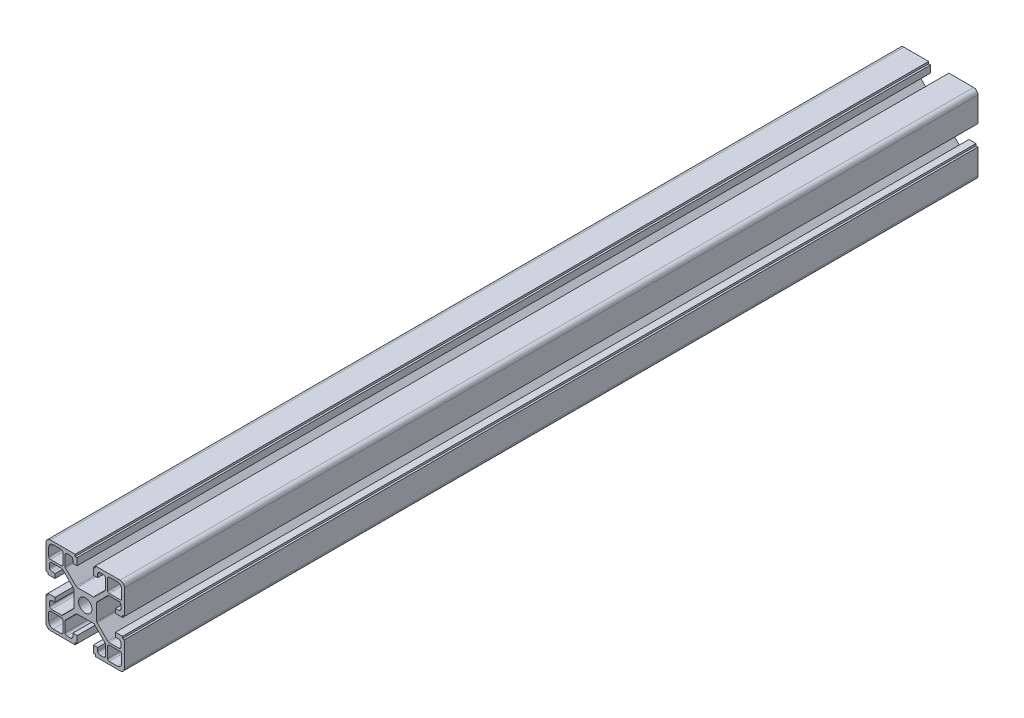
SolidWorks part; units mm, degrees
material "6063-T5"
ref_plane "Front Plane" through (0, 0, 0) normal (0, 0, 1) x (1, 0, 0)
ref_plane "Top Plane" through (0, 0, 0) normal (0, 1, 0) x (1, 0, 0)
ref_plane "Right Plane" through (0, 0, 0) normal (1, 0, 0) x (0, 0, -1)
sketch "Sketch1" plane through (0, 0, 0) normal (0, 0, 1) x (1, 0, 0)
  line L4 (20, 17.75) -> (20, 5.15)
  line L5 (0, -17.7813) -> (0, 18.2) construction
  line L6 (0, 0) -> (38.8613, 0) construction
  line L8 (18.6, 16.35) -> (18.6, 12.2)
  line L10 (11.4, 17.8) -> (11.4, 12.2)
  line L11 (-4.1, 5.85) -> (4.1, 5.85)
  line L14 (5.85, 4.1089) -> (5.85, -4.1089)
  line L17 (12.2, 11.4) -> (17.8, 11.4)
  line L24 (4.15, 19) -> (4.15, 15.4)
  line L25 (4.15, 15.4) -> (6.35, 15.4)
  line L26 (6.35, 15.4) -> (6.35, 16.95)
  line L27 (10.3, 17.2) -> (10.3, 12.0545)
  line L28 (10.0659, 11.489) -> (4.6659, 6.0845)
  line L29 (6.0841, 4.6743) -> (11.4708, 10.0655)
  line L30 (12.0367, 10.3) -> (17.2, 10.3)
  line L31 (18.2, 9.3) -> (18.2, 7.6)
  line L32 (16.95, 6.35) -> (15.4, 6.35)
  line L33 (15.4, 6.35) -> (15.4, 4.15)
  line L34 (15.4, 4.15) -> (19, 4.15)
  line L35 (18.6, 18.6) -> (18.6, -18.6) construction
  line L36 (-18.6, 18.6) -> (18.6, 18.6) construction
  line L37 (-20, 20) -> (20, 20) construction
  line L38 (20, 20) -> (20, -20) construction
  line L40 (7.6, 18.2) -> (9.3, 18.2)
  line L42 (4.15, 19) -> (5.15, 19)
  line L43 (5.15, 19) -> (5.15, 20)
  line L56 (-18.6, 18.6) -> (-18.6, -18.6) construction
  line L57 (-20, 20) -> (-20, -20) construction
  line L60 (5.15, 20) -> (17.75, 20)
  line L91 (-18.6, -18.6) -> (18.6, -18.6) construction
  line L92 (-20, -20) -> (20, -20) construction
  line L93 (12.2, 18.6) -> (16.35, 18.6)
  line L94 (17.9399, 17.9421) -> (20, 20) construction
  line L95 (0, 0) -> (11.4, 11.4094) construction
  line L101 (19, 4.15) -> (19, 5.15)
  line L102 (19, 5.15) -> (20, 5.15)
  line L104 (-5.85, 4.1089) -> (-5.85, -4.1089)
  line L105 (-19, 5.15) -> (-20, 5.15)
  line L106 (-19, 4.15) -> (-19, 5.15)
  line L107 (-12.2, 18.6) -> (-16.35, 18.6)
  line L108 (-5.15, 20) -> (-17.75, 20)
  line L109 (-5.15, 19) -> (-5.15, 20)
  line L110 (-4.15, 19) -> (-5.15, 19)
  line L111 (-7.6, 18.2) -> (-9.3, 18.2)
  line L112 (-15.4, 4.15) -> (-19, 4.15)
  line L113 (-15.4, 6.35) -> (-15.4, 4.15)
  line L114 (-16.95, 6.35) -> (-15.4, 6.35)
  line L115 (-18.2, 9.3) -> (-18.2, 7.6)
  line L116 (-12.0367, 10.3) -> (-17.2, 10.3)
  line L117 (-6.0841, 4.6743) -> (-11.4708, 10.0655)
  line L118 (-10.0659, 11.489) -> (-4.6659, 6.0845)
  line L119 (-10.3, 17.2) -> (-10.3, 12.0545)
  line L120 (-6.35, 15.4) -> (-6.35, 16.95)
  line L121 (-4.15, 15.4) -> (-6.35, 15.4)
  line L122 (-4.15, 19) -> (-4.15, 15.4)
  line L123 (-12.2, 11.4) -> (-17.8, 11.4)
  line L124 (-11.4, 17.8) -> (-11.4, 12.2)
  line L125 (-18.6, 16.35) -> (-18.6, 12.2)
  line L126 (-20, 17.75) -> (-20, 5.15)
  line L127 (-20, -17.75) -> (-20, -5.15)
  line L128 (-18.6, -16.35) -> (-18.6, -12.2)
  line L129 (-11.4, -17.8) -> (-11.4, -12.2)
  line L130 (-12.2, -11.4) -> (-17.8, -11.4)
  line L131 (-4.15, -19) -> (-4.15, -15.4)
  line L132 (-4.15, -15.4) -> (-6.35, -15.4)
  line L133 (-6.35, -15.4) -> (-6.35, -16.95)
  line L134 (-10.3, -17.2) -> (-10.3, -12.0545)
  line L135 (-10.0659, -11.489) -> (-4.6659, -6.0845)
  line L136 (-6.0841, -4.6743) -> (-11.4708, -10.0655)
  line L137 (-12.0367, -10.3) -> (-17.2, -10.3)
  line L138 (-18.2, -9.3) -> (-18.2, -7.6)
  line L139 (-16.95, -6.35) -> (-15.4, -6.35)
  line L140 (-15.4, -6.35) -> (-15.4, -4.15)
  line L141 (-15.4, -4.15) -> (-19, -4.15)
  line L142 (-7.6, -18.2) -> (-9.3, -18.2)
  line L143 (-4.15, -19) -> (-5.15, -19)
  line L144 (-5.15, -19) -> (-5.15, -20)
  line L145 (-5.15, -20) -> (-17.75, -20)
  line L146 (-12.2, -18.6) -> (-16.35, -18.6)
  line L147 (-19, -4.15) -> (-19, -5.15)
  line L148 (-19, -5.15) -> (-20, -5.15)
  line L149 (19, -5.15) -> (20, -5.15)
  line L150 (19, -4.15) -> (19, -5.15)
  line L151 (12.2, -18.6) -> (16.35, -18.6)
  line L152 (5.15, -20) -> (17.75, -20)
  line L153 (5.15, -19) -> (5.15, -20)
  line L154 (4.15, -19) -> (5.15, -19)
  line L155 (7.6, -18.2) -> (9.3, -18.2)
  line L156 (15.4, -4.15) -> (19, -4.15)
  line L157 (15.4, -6.35) -> (15.4, -4.15)
  line L158 (16.95, -6.35) -> (15.4, -6.35)
  line L159 (18.2, -9.3) -> (18.2, -7.6)
  line L160 (12.0367, -10.3) -> (17.2, -10.3)
  line L161 (6.0841, -4.6743) -> (11.4708, -10.0655)
  line L162 (10.0659, -11.489) -> (4.6659, -6.0845)
  line L163 (10.3, -17.2) -> (10.3, -12.0545)
  line L164 (6.35, -15.4) -> (6.35, -16.95)
  line L165 (4.15, -15.4) -> (6.35, -15.4)
  line L166 (4.15, -19) -> (4.15, -15.4)
  line L167 (12.2, -11.4) -> (17.8, -11.4)
  line L168 (-4.1, -5.85) -> (4.1, -5.85)
  line L169 (11.4, -17.8) -> (11.4, -12.2)
  line L170 (18.6, -16.35) -> (18.6, -12.2)
  line L171 (20, -17.75) -> (20, -5.15)
  circle A0 centre (0, 0) radius 3.4
  arc A7 (16.35, 18.6) -> (18.6, 16.35) centre (16.35, 16.35) cw
  arc A8 (20, 17.75) -> (17.75, 20) centre (17.75, 17.75) ccw
  arc A9 (6.35, 16.95) -> (7.6, 18.2) centre (7.6, 16.95) cw
  arc A10 (18.2, 7.6) -> (16.95, 6.35) centre (16.95, 7.6) cw
  arc A11 (17.2, 10.3) -> (18.2, 9.3) centre (17.2, 9.3) cw
  arc A12 (9.3, 18.2) -> (10.3, 17.2) centre (9.3, 17.2) cw
  arc A13 (4.6659, 6.0845) -> (4.1, 5.85) centre (4.1, 6.65) cw
  arc A14 (6.0841, 4.6743) -> (5.85, 4.1089) centre (6.65, 4.1089) ccw
  arc A15 (17.8, 11.4) -> (18.6, 12.2) centre (17.8, 12.2) ccw
  arc A16 (12.2, 18.6) -> (11.4, 17.8) centre (12.2, 17.8) ccw
  arc A17 (11.4, 12.2) -> (12.2, 11.4) centre (12.2, 12.2) ccw
  arc A18 (11.4708, 10.0655) -> (12.0367, 10.3) centre (12.0367, 9.5) cw
  arc A19 (10.3, 12.0545) -> (10.0659, 11.489) centre (9.5, 12.0545) cw
  arc A20 (-10.3, 12.0545) -> (-10.0659, 11.489) centre (-9.5, 12.0545) ccw
  arc A21 (-11.4708, 10.0655) -> (-12.0367, 10.3) centre (-12.0367, 9.5) ccw
  arc A22 (-11.4, 12.2) -> (-12.2, 11.4) centre (-12.2, 12.2) cw
  arc A23 (-12.2, 18.6) -> (-11.4, 17.8) centre (-12.2, 17.8) cw
  arc A24 (-17.8, 11.4) -> (-18.6, 12.2) centre (-17.8, 12.2) cw
  arc A25 (-6.0841, 4.6743) -> (-5.85, 4.1089) centre (-6.65, 4.1089) cw
  arc A26 (-4.6659, 6.0845) -> (-4.1, 5.85) centre (-4.1, 6.65) ccw
  arc A27 (-9.3, 18.2) -> (-10.3, 17.2) centre (-9.3, 17.2) ccw
  arc A28 (-17.2, 10.3) -> (-18.2, 9.3) centre (-17.2, 9.3) ccw
  arc A29 (-18.2, 7.6) -> (-16.95, 6.35) centre (-16.95, 7.6) ccw
  arc A30 (-6.35, 16.95) -> (-7.6, 18.2) centre (-7.6, 16.95) ccw
  arc A31 (-20, 17.75) -> (-17.75, 20) centre (-17.75, 17.75) cw
  arc A32 (-16.35, 18.6) -> (-18.6, 16.35) centre (-16.35, 16.35) ccw
  arc A33 (-16.35, -18.6) -> (-18.6, -16.35) centre (-16.35, -16.35) cw
  arc A34 (-20, -17.75) -> (-17.75, -20) centre (-17.75, -17.75) ccw
  arc A35 (-6.35, -16.95) -> (-7.6, -18.2) centre (-7.6, -16.95) cw
  arc A36 (-18.2, -7.6) -> (-16.95, -6.35) centre (-16.95, -7.6) cw
  arc A37 (-17.2, -10.3) -> (-18.2, -9.3) centre (-17.2, -9.3) cw
  arc A38 (-9.3, -18.2) -> (-10.3, -17.2) centre (-9.3, -17.2) cw
  arc A39 (-4.6659, -6.0845) -> (-4.1, -5.85) centre (-4.1, -6.65) cw
  arc A40 (-6.0841, -4.6743) -> (-5.85, -4.1089) centre (-6.65, -4.1089) ccw
  arc A41 (-17.8, -11.4) -> (-18.6, -12.2) centre (-17.8, -12.2) ccw
  arc A42 (-12.2, -18.6) -> (-11.4, -17.8) centre (-12.2, -17.8) ccw
  arc A43 (-11.4, -12.2) -> (-12.2, -11.4) centre (-12.2, -12.2) ccw
  arc A44 (-11.4708, -10.0655) -> (-12.0367, -10.3) centre (-12.0367, -9.5) cw
  arc A45 (-10.3, -12.0545) -> (-10.0659, -11.489) centre (-9.5, -12.0545) cw
  arc A46 (10.3, -12.0545) -> (10.0659, -11.489) centre (9.5, -12.0545) ccw
  arc A47 (11.4708, -10.0655) -> (12.0367, -10.3) centre (12.0367, -9.5) ccw
  arc A48 (11.4, -12.2) -> (12.2, -11.4) centre (12.2, -12.2) cw
  arc A49 (12.2, -18.6) -> (11.4, -17.8) centre (12.2, -17.8) cw
  arc A50 (17.8, -11.4) -> (18.6, -12.2) centre (17.8, -12.2) cw
  arc A51 (6.0841, -4.6743) -> (5.85, -4.1089) centre (6.65, -4.1089) cw
  arc A52 (4.6659, -6.0845) -> (4.1, -5.85) centre (4.1, -6.65) ccw
  arc A53 (9.3, -18.2) -> (10.3, -17.2) centre (9.3, -17.2) ccw
  arc A54 (17.2, -10.3) -> (18.2, -9.3) centre (17.2, -9.3) ccw
  arc A55 (18.2, -7.6) -> (16.95, -6.35) centre (16.95, -7.6) ccw
  arc A56 (6.35, -16.95) -> (7.6, -18.2) centre (7.6, -16.95) ccw
  arc A57 (20, -17.75) -> (17.75, -20) centre (17.75, -17.75) cw
  arc A58 (16.35, -18.6) -> (18.6, -16.35) centre (16.35, -16.35) ccw
  point P0 (0, 0)
  point P16 (-5.85, 0)
  point P66 (0, 5.85)
  point P120 (5.85, 0)
  point P218 (0, -5.85)
  dimension "D5" = 6.8
  dimension "D6" = 1.4
  dimension "D15" = 5.85
  dimension "D44" = 2.25
  dimension "D25" = 1.25
  dimension "D26" = 1
  dimension "D27" = 0.8
  dimension "D7" = 1.1
  dimension "D8" = 1.1
  dimension "D9" = 1.8
  dimension "D10" = 2.2
  dimension "D11" = 4.6
  dimension "D12" = 1.8
  dimension "D13" = 2.2
  dimension "D14" = 5.85
  dimension "D16" = 1.4
  dimension "D17" = 4.15
  dimension "D18" = 1
  dimension "D19" = 1
  dimension "D20" = 10.3
  dimension "D21" = 4.15
  dimension "D22" = 2
  dimension "D23" = 45.024
  dimension "D24" = 1
  dimension "D41" = 10.3
  dimension "D60" = 14.15
  dimension "D73" = 1
  dimension "D74" = 1
  dimension "D82" = 14.15
  dimension "D3" = 4.6
extrude "Boss-Extrude1" add sketch "Sketch1" along normal blind 713
sketch "Sketch2" plane through (0, 20, 0) normal (0, 1, 0) x (1, 0, 0)
  line L0 (-20, -713) -> (-20, 0) construction
  line L1 (-20, -435) -> (20, -435)
  line L2 (-20, -435) -> (-20, -713)
  line L3 (-20, -713) -> (20, -713)
  line L4 (20, -435) -> (20, -713)
  line L5 (-5.15, 0) -> (-17.75, 0) construction
  dimension "D1" = 435
extrude "Cut-Extrude1" cut sketch "Sketch2" against normal through all
